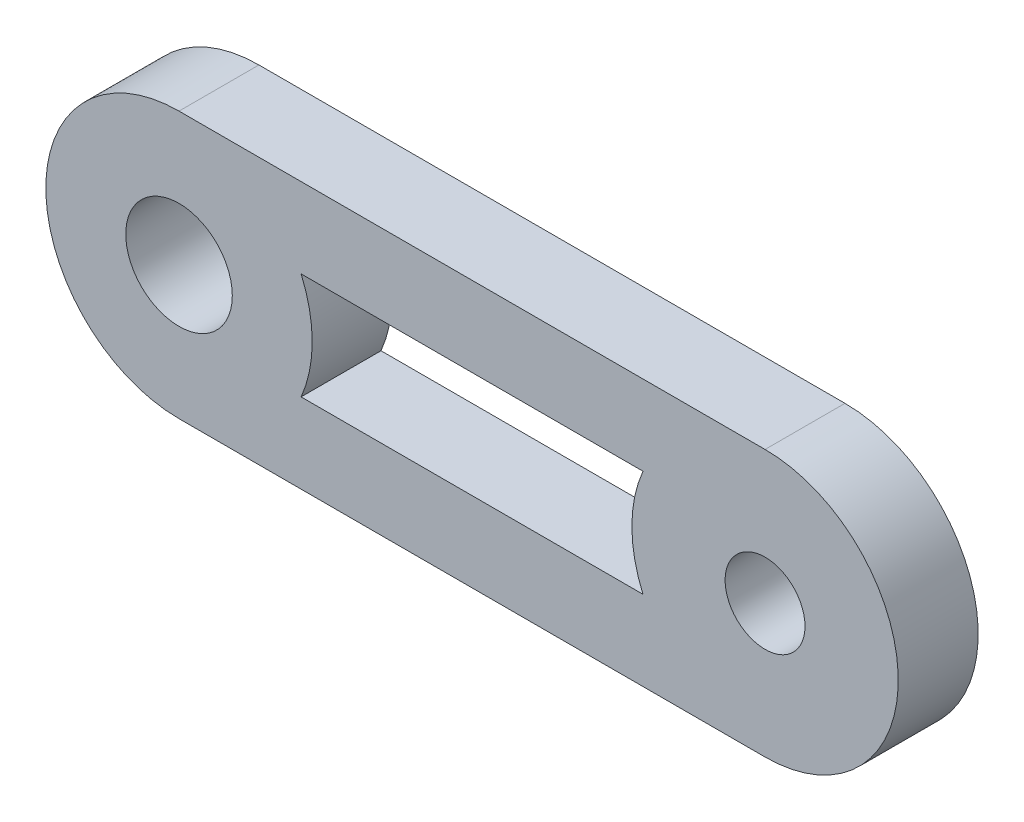
SolidWorks part; units mm, degrees
material "Plain Carbon Steel"
ref_plane "Front Plane" through (0, 0, 0) normal (0, 0, 1) x (1, 0, 0)
ref_plane "Top Plane" through (0, 0, 0) normal (0, 1, 0) x (1, 0, 0)
ref_plane "Right Plane" through (0, 0, 0) normal (1, 0, 0) x (0, 0, -1)
sketch "Sketch1" plane through (0, 0, 0) normal (0, 0, 1) x (1, 0, 0)
  line L0 (0, 0) -> (22, 0)
  line L1 (0, -5) -> (22, -5)
  line L2 (0, 5) -> (22, 5)
  circle A0 centre (22, 0) radius 1.5
  circle A1 centre (0, 0) radius 1.5
  arc A2 (0, -5) -> (0, 5) centre (0, 0) cw
  arc A3 (22, -5) -> (22, 5) centre (22, 0) ccw
  dimension "D1" = 3
extrude "Extrude1" add sketch "Sketch1" along normal blind 3 contours L1 A3 L2 A2 A1 A0 region at (-4.6647, 0, 0)
sketch "Sketch2" plane through (0, 0, 3) normal (0, 0, 1) x (1, 0, 0)
  line L4 (0, -2) -> (22, -2)
  line L5 (22, 2) -> (0, 2)
  line L6 (4.5826, -2) -> (17.4174, -2)
  line L7 (17.4174, 2) -> (4.5826, 2)
  circle A0 centre (0, 0) radius 2
  arc A2 (4.5826, -2) -> (4.5826, 2) centre (0, 0) ccw
  arc A3 (17.4174, 2) -> (17.4174, -2) centre (22, 0) ccw
  arc A4 (22, -2) -> (22, 2) centre (22, 0) ccw
  arc A5 (0, 2) -> (0, -2) centre (0, 0) ccw
  dimension "D2" = 4
  dimension "D1" = 3
extrude "Cut-Extrude1" cut sketch "Sketch2" against normal blind 10
move or copy body "Body-Move/Copy1" [suppressed] bodies to move or copy 103
move or copy body "Body-Move/Copy2" [suppressed] bodies to move or copy 103
move or copy body "Body-Move/Copy3" [suppressed] bodies to move or copy 103
